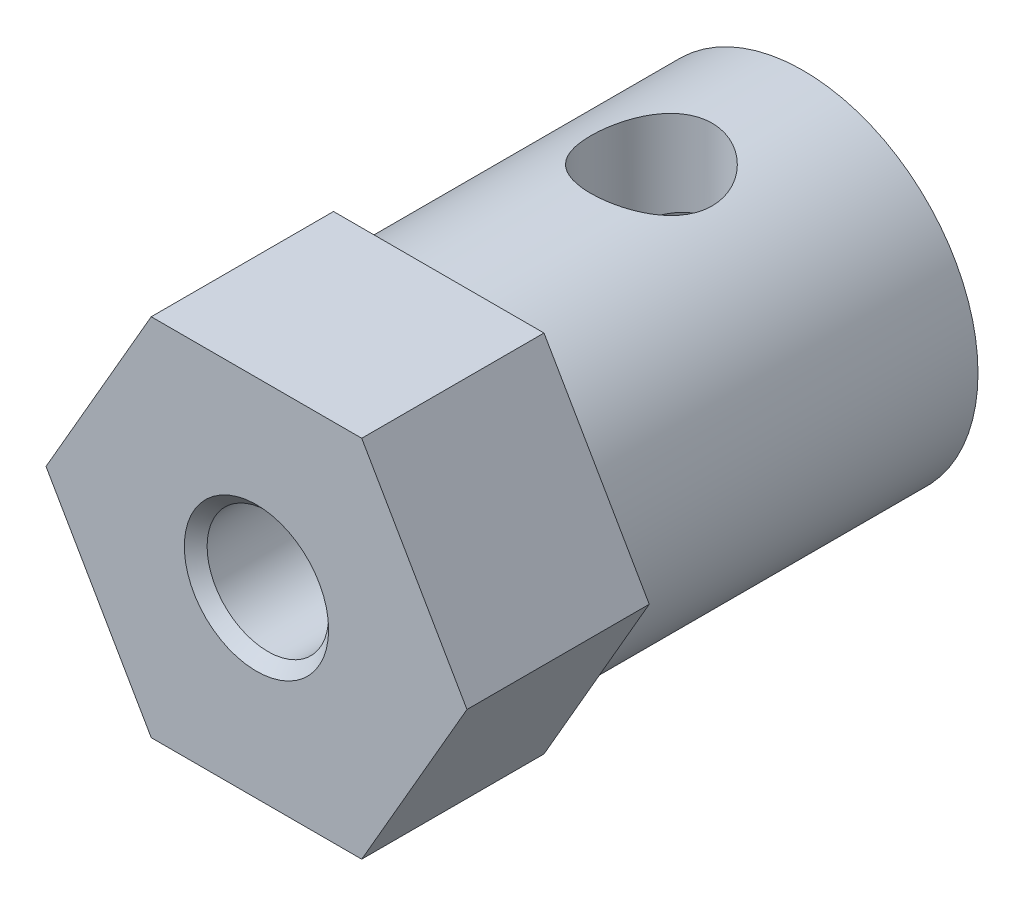
SolidWorks part; units mm, degrees
ref_plane "前视基准面" through (0, 0, 0) normal (0, 0, 1) x (1, 0, 0)
ref_plane "上视基准面" through (0, 0, 0) normal (0, 1, 0) x (1, 0, 0)
ref_plane "右视基准面" through (0, 0, 0) normal (1, 0, 0) x (0, 0, -1)
other "Configuration Table"
ref_plane "基准面1" through (0, 0, 6) normal (0, 0, 1) x (1, 0, 0)
sketch "草图1" plane through (0, 0, 6) normal (0, 0, 1) x (1, 0, 0)
  line L0 (-3.4641, -6) -> (3.4641, -6)
  line L1 (3.4641, -6) -> (6.9282, 0)
  line L2 (6.9282, 0) -> (3.4641, 6)
  line L3 (3.4641, 6) -> (-3.4641, 6)
  line L4 (-3.4641, 6) -> (-6.9282, 0)
  line L5 (-6.9282, 0) -> (-3.4641, -6)
extrude "凸台-拉伸1" add sketch "草图1" against normal blind 6
sketch "草图2" plane through (0, 0, 0) normal (0, 1, 0) x (1, 0, 0)
  line L0 (5.75, 12) -> (0, 12)
  line L1 (0, 12) -> (0, 0)
  line L2 (0, 0) -> (5.75, 0)
  line L3 (5.75, 0) -> (5.75, 12)
  line L4 (0, 12) -> (0, 0) construction
  line L5 (-55, -6) -> (55, -6) construction
  dimension "D1" = 5.75
  dimension "D2" = 18
revolve "旋转1" add sketch "草图2" angle 360 about L4 reverse direction yes
hole_wizard "M4 六角头机械螺钉的柱形沉头孔1" positions "草图4" profile "草图3" counterbore size "M3" standard "ANSI Metric"
sketch "草图4" plane through (0, 0, -12) normal (0, 0, -1) x (-1, 0, 0)
  point P0 (0, 0)
sketch "草图3" plane through (0, 0, -12) normal (1, 0, 0) x (0, 1, 0)
  line L0 (0, 0) -> (0, 18)
  line L1 (0, 18) -> (2, 18)
  line L3 (2, 18) -> (2, 12)
  line L4 (2, 12) -> (3, 12)
  line L5 (3, 12) -> (3, 0)
  line L7 (3, 0) -> (0, 0)
  line L11 (0, -6.35) -> (0, 107.95) construction
  dimension "通孔孔直径" = 4
  dimension "通孔孔深度" = 18
  dimension "柱形沉头孔直径" = 6
  dimension "柱形沉头孔深度" = 12
ref_plane "基准面2" through (0, 5.75, 0) normal (0, 1, 0) x (1, 0, 0)
sketch "草图7" plane through (0, 5.75, 0) normal (0, 1, 0) x (1, 0, 0)
  line L0 (0, 12) -> (0, -6) construction
  line L1 (3, 12) -> (-3, 12) construction
  line L2 (-55, -6) -> (55, -6) construction
  line L3 (5.75, 12) -> (-5.75, 12) construction
  circle A0 centre (0, 7) radius 2
  point P7 (0, 7)
  dimension "D2" = 4
  dimension "D1" = 5
extrude "切除-拉伸1" cut sketch "草图7" against normal through all
chamfer "倒角1" distance 0.375 angle 45 1 edges at (-2, 0, 6)
